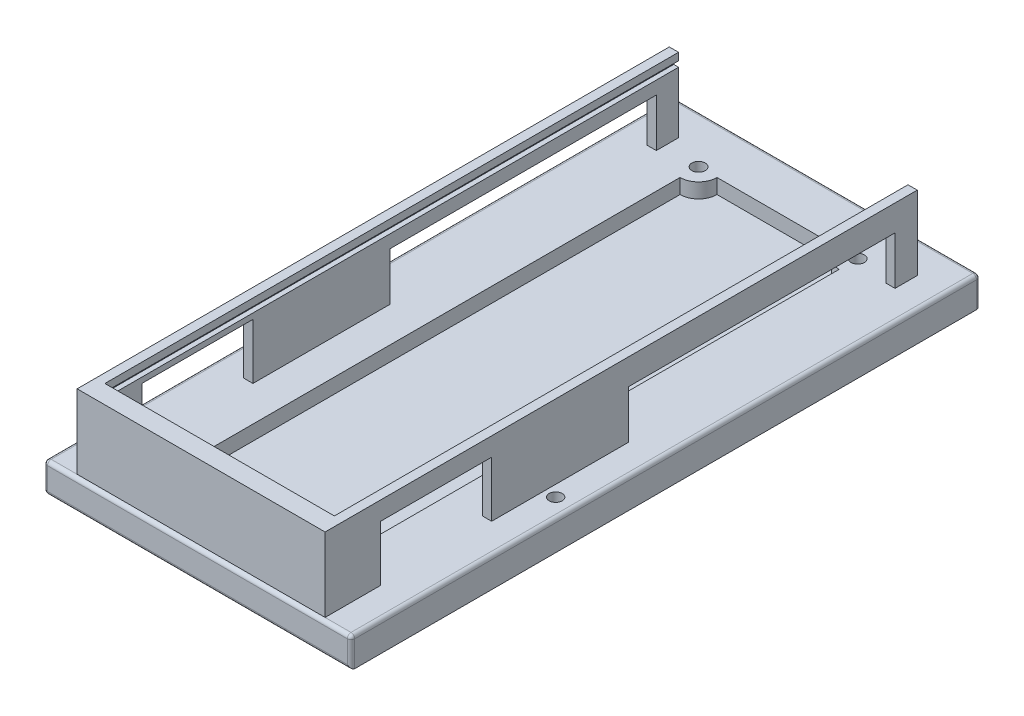
SolidWorks part; units mm, degrees
ref_plane "Front Plane" through (0, 0, 0) normal (0, 0, 1) x (1, 0, 0)
ref_plane "Top Plane" through (0, 0, 0) normal (0, 1, 0) x (1, 0, 0)
ref_plane "Right Plane" through (0, 0, 0) normal (1, 0, 0) x (0, 0, -1)
sketch "Sketch1" plane through (0, 0, 0) normal (0, 1, 0) x (1, 0, 0)
  line L0 (41.5, 95) -> (41.5, 0) construction
  line L1 (0, 0) -> (83, 0)
  line L2 (0, 0) -> (0, 170)
  line L3 (0, 170) -> (83, 170)
  line L4 (83, 0) -> (83, 170)
  line L5 (20, 156.9) -> (20, 13.1) construction
  circle A0 centre (5, 60.3) radius 1.75
  circle A1 centre (20, 13.1) radius 1.65 construction
  circle A2 centre (20, 156.9) radius 1.65 construction
  circle A3 centre (78, 60.3) radius 1.75
  circle A4 centre (63, 13.1) radius 1.65 construction
  circle A5 centre (63, 156.9) radius 1.65 construction
  point P19 (20, 85)
  point P20 (41.5, 0)
  point P21 (0, 85)
  dimension "D2" = 36.5
  dimension "D3" = 3.5
  dimension "D5" = 47.2
  dimension "D6" = 21.5
  dimension "D7" = 3.3
  dimension "D9" = 143.8
  dimension "D10" = 3.3
  dimension "D1" = 83
  dimension "D4" = 170
extrude "Boss-Extrude1" add sketch "Sketch1" along normal blind 8
sketch "Sketch3" plane through (0, 0, 0) normal (0, -1, 0) x (1, 0, 0)
  point P0 (20, -13.1)
  point P1 (63, -13.1)
  point P3 (63, -156.9)
  point P5 (20, -156.9)
hole_wizard "CBORE for M3 SHCS1" positions "Sketch3" profile "Sketch4" counterbore size "M3" standard "ANSI Metric" end condition through all
sketch "Sketch4" plane through (20, 0, -13.1) normal (1, 0, 0) x (0, 0, -1)
  line L0 (0, 0) -> (0, 8)
  line L1 (0, 8) -> (1.8, 8)
  line L3 (1.8, 8) -> (1.8, 3)
  line L4 (1.8, 3) -> (3.25, 3)
  line L5 (3.25, 3) -> (3.25, 0)
  line L7 (3.25, 0) -> (0, 0)
  line L11 (0, -6.35) -> (0, 107.95) construction
  dimension "Thru Hole Dia." = 3.6
  dimension "Thru Hole Depth" = 8
  dimension "C'Bore Dia." = 6.5
  dimension "C'Bore Depth" = 3
sketch "Sketch5" plane through (0, 8, 0) normal (0, 1, 0) x (1, 0, 0)
  line L5 (25, 156.9) -> (58, 156.9)
  line L6 (20, 151.9) -> (20, 18.1)
  line L11 (25, 13.1) -> (58, 13.1)
  line L12 (63, 151.9) -> (63, 18.1)
  arc A0 (20, 151.9) -> (25, 156.9) centre (20, 156.9) ccw
  arc A1 (58, 156.9) -> (63, 151.9) centre (63, 156.9) ccw
  arc A2 (63, 18.1) -> (58, 13.1) centre (63, 13.1) ccw
  arc A7 (25, 13.1) -> (20, 18.1) centre (20, 13.1) ccw
  point P0 (20, 156.9)
  point P1 (63, 156.9)
  point P2 (63, 13.1)
  point P3 (20, 13.1)
extrude "Cut-Extrude1" cut sketch "Sketch5" against normal blind 4
sketch "Sketch6" plane through (0, 0, 0) normal (0, -1, 0) x (1, 0, 0)
  line L1 (12, -95) -> (17, -95)
  line L2 (12, -95) -> (12, -115)
  line L3 (12, -115) -> (17, -115)
  line L4 (17, -95) -> (17, -115)
  dimension "D1" = 5
  dimension "D2" = 20
  dimension "D3" = 8
  dimension "D4" = 34.7
extrude "Boss-Extrude2" add sketch "Sketch6" along normal blind 8.8
sketch "Sketch7" plane through (0, 0, -115) normal (0, 0, -1) x (-1, 0, 0)
  line L0 (-17, -8.8) -> (-17, 0) construction
  line L1 (-12, 0) -> (-15.2, 0)
  line L2 (-12, 0) -> (-12, -6.8)
  line L3 (-12, -6.8) -> (-15.2, -6.8)
  line L4 (-15.2, 0) -> (-15.2, -6.8)
  dimension "D1" = 6.8
  dimension "D2" = 1.8
extrude "Cut-Extrude2" cut sketch "Sketch7" against normal through all
fillet "Fillet1" radius 6 1 edges at (17, 0, -105) second distance 8 first distance on face at (41.5, 0, -85)
fillet "Fillet2" radius 1 10 edges at (0, 4, 0) (41.5, 8, 0) (83, 4, 0) (83, 4, -170) (83, 8, -85) (41.5, 8, -170) (0, 4, -170) (0, 8, -85) (0, 0, -85) (41.5, 0, 0)
sketch "Sketch8" plane through (0, 8, 0) normal (0, 1, 0) x (1, 0, 0)
  line L1 (8, 161) -> (75, 161)
  line L2 (8, 161) -> (8, 1)
  line L3 (8, 1) -> (75, 1)
  line L4 (75, 161) -> (75, 1)
  line L6 (1, 1) -> (82, 1) construction
  circle A4 centre (5, 60.3) radius 1.75 construction
  dimension "D1" = 3
  dimension "D3" = 160
  dimension "D2" = 3
  dimension "D4" = 0
extrude "Boss-Extrude4" add sketch "Sketch8" along normal blind 20
sketch "Sketch11" plane through (0, 0, -161) normal (0, 0, -1) x (-1, 0, 0)
  line L0 (-75, 8) -> (-8, 8) construction
  line L1 (-72.5, 8) -> (-10.5, 8)
  line L2 (-72.5, 8) -> (-72.5, 24.5)
  line L3 (-72.5, 28) -> (-10.5, 28)
  line L4 (-10.5, 8) -> (-10.5, 24.5)
  line L5 (-75, 28) -> (-75, 8) construction
  line L6 (-8, 28) -> (-8, 8) construction
  line L7 (-75, 28) -> (-8, 28) construction
  line L8 (-10.5, 24.5) -> (-9.2, 24.5)
  line L9 (-73.8, 26) -> (-72.5, 26)
  line L10 (-73.8, 26) -> (-73.8, 24.5)
  line L11 (-73.8, 24.5) -> (-72.5, 24.5)
  line L12 (-9.2, 26) -> (-9.2, 24.5)
  line L13 (-10.5, 26) -> (-9.2, 26)
  line L14 (-72.5, 26) -> (-72.5, 28)
  line L15 (-10.5, 26) -> (-10.5, 28)
  dimension "D1" = 2.5
  dimension "D2" = 2.5
  dimension "D3" = 0
  dimension "D4" = 1.2
  dimension "D5" = 1.5
  dimension "D6" = 1.2
  dimension "D7" = 2
extrude "Cut-Extrude3" cut sketch "Sketch11" against normal blind 155
sketch "Sketch12" plane through (0, 0, -6) normal (0, 0, -1) x (-1, 0, 0)
  line L1 (-73.8, 26) -> (-9.2, 26)
  line L2 (-73.8, 26) -> (-73.8, 24.5)
  line L3 (-73.8, 24.5) -> (-9.2, 24.5)
  line L4 (-9.2, 26) -> (-9.2, 24.5)
extrude "Cut-Extrude4" cut sketch "Sketch12" against normal blind 1
sketch "Sketch15" plane through (75, 0, 0) normal (1, 0, 0) x (0, 0, -1)
  line L0 (1, 8) -> (169, 8) construction
  line L1 (128, 8) -> (110, 8)
  line L2 (128, 8) -> (128, 21) construction
  line L3 (128, 21) -> (110, 21)
  line L4 (110, 8) -> (110, 21) construction
  line L5 (101, 21) -> (110, 21)
  line L6 (1, 8) -> (161, 8) construction
  line L7 (101, 8) -> (83, 8)
  line L8 (101, 8) -> (101, 21) construction
  line L9 (101, 21) -> (83, 21)
  line L10 (83, 8) -> (83, 21)
  line L12 (101, 8) -> (110, 8)
  line L13 (128, 21) -> (137, 21)
  line L14 (137, 21) -> (155, 21)
  line L15 (137, 21) -> (137, 8) construction
  line L16 (137, 8) -> (155, 8)
  line L17 (155, 21) -> (155, 8)
  line L18 (128, 8) -> (137, 8)
  line L20 (161, 28) -> (161, 8) construction
  dimension "D1" = 18
  dimension "D2" = 13
  dimension "D3" = 6
  dimension "D4" = 18
  dimension "D5" = 13
  dimension "D6" = 9
  dimension "D7" = 18
  dimension "D8" = 13
  dimension "D9" = 9
extrude "Cut-Extrude5" cut sketch "Sketch15" against normal through all and the other way through all
sketch "Sketch16" plane through (75, 0, 0) normal (1, 0, 0) x (0, 0, -1)
  line L0 (1, 8) -> (169, 8) construction
  line L1 (16, 8) -> (46, 8)
  line L2 (16, 8) -> (16, 23)
  line L3 (16, 23) -> (46, 23)
  line L4 (46, 8) -> (46, 23)
  line L5 (1, 28) -> (1, 8) construction
  point P8 (16, 15.5)
  dimension "D1" = 15
  dimension "D2" = 30
  dimension "D3" = 15
extrude "Cut-Extrude6" cut sketch "Sketch16" against normal through all
